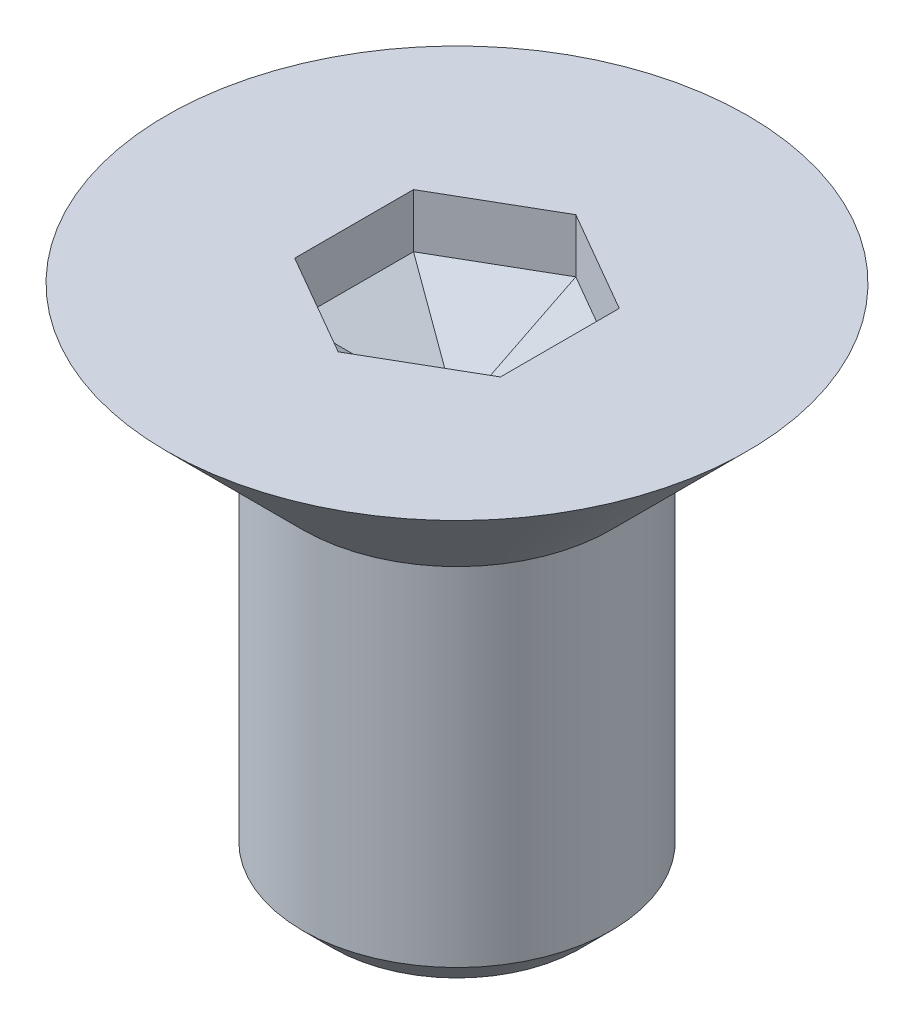
SolidWorks part; units mm, degrees
ref_plane "前视基准面" through (0, 0, 0) normal (0, 0, 1) x (1, 0, 0)
ref_plane "上视基准面" through (0, 0, 0) normal (0, 1, 0) x (1, 0, 0)
ref_plane "右视基准面" through (0, 0, 0) normal (1, 0, 0) x (0, 0, -1)
sketch "草图2" plane through (0, 0, 0) normal (0, 0, 1) x (1, 0, 0)
  line L0 (0, -3.72) -> (0, 0)
  line L1 (0, 0) -> (5.65, 0)
  line L2 (5.65, 0) -> (1.93, -3.72)
  line L3 (1.93, -3.72) -> (0, -3.72)
  dimension "D1" = 45
  dimension "k" = 3.72
  dimension "dk/2" = 5.65
revolve "旋转1" add sketch "草图2" angle 360 about L0
sketch "草图4" plane through (0, 0, 0) normal (0, -1, 0) x (1, 0, 0)
  circle A0 centre (0, 0) radius 3
  dimension "d" = 6
extrude "凸台-拉伸2" add sketch "草图4" along normal blind 10
cosmetic thread "装饰螺纹线1" parameters "D2"=1.221
sketch "草图3" plane through (0, 0, 0) normal (0, 1, 0) x (1, 0, 0)
  line L1 (2, 1.1547) -> (0, 2.3094)
  line L2 (0, 2.3094) -> (-2, 1.1547)
  line L3 (-2, 1.1547) -> (-2, -1.1547)
  line L4 (-2, -1.1547) -> (0, -2.3094)
  line L5 (0, -2.3094) -> (2, -1.1547)
  line L6 (2, -1.1547) -> (2, 1.1547)
  circle A0 centre (0, 0) radius 2 construction
  dimension "S" = 4
extrude "切除-拉伸1" cut sketch "草图3" against normal blind 2.2
chamfer "倒角3" distance 1.1527 angle 60 6 edges at (-1, -2.2, 1.7321) (-2, -2.2, 0) (-1, -2.2, -1.7321) (1, -2.2, -1.7321) (2, -2.2, 0) (1, -2.2, 1.7321) first distance on face at (-1, -1.1, 1.7321) first distance on face at (-2, -1.1, 0) first distance on face at (-1, -1.1, -1.7321) first distance on face at (1, -1.1, -1.7321) first distance on face at (2, -1.1, 0) first distance on face at (1, -1.1, 1.7321)
chamfer "倒角4" distance 0.6 angle 45 1 edges at (0, -10, -3)
ref_axis "基准轴1" through (0, -9.4, 0) along (0, 1, 0)
ref_plane "基准面1" through (0, 0, 0) normal (0, -1, 0) x (-1, 0, 0)
equation "\"D1@倒角3\"= \"S@草图3\" / 3.47"
equation "\"D1@倒角4\"= \"d@草图4\" / 10"
